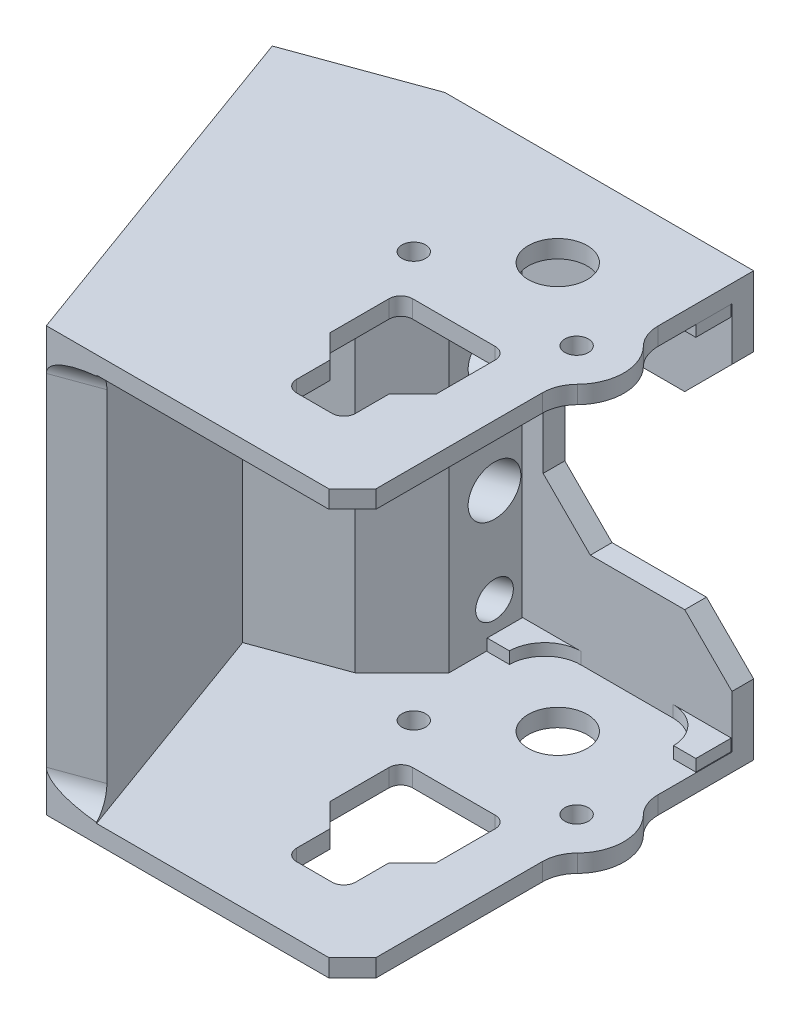
SolidWorks part; units mm, degrees
note: The reader was unsure of these and kept them because the rebuilt part matched: shared geometry of "Sketch15<2>", "Sketch16<2>".
ref_plane "Płaszczyzna przednia" through (0, 0, 0) normal (0, 0, 1) x (1, 0, 0)
ref_plane "Płaszczyzna górna" through (0, 0, 0) normal (0, 1, 0) x (1, 0, 0)
ref_plane "Płaszczyzna prawa" through (0, 0, 0) normal (1, 0, 0) x (0, 0, -1)
sketch "Sketch1" plane through (0, 0, 0) normal (0, 1, 0) x (1, 0, 0)
  line L0 (-6.9, 0) -> (6.9, 0) construction
  line L2 (-8.9, 13) -> (8.9, 13)
  line L3 (-8.9, 13) -> (-8.9, -17)
  line L4 (-8.9, -17) -> (8.9, -17)
  line L5 (8.9, 13) -> (8.9, -17)
  circle A0 centre (-6.9, 0) radius 1
  circle A1 centre (6.9, 0) radius 1
  circle A2 centre (6.9, 0) radius 2 construction
  circle A3 centre (-6.9, 0) radius 2 construction
  circle A4 centre (0, 5.3) radius 2.5
  point P4 (0, 0)
  dimension "D2" = 2
  dimension "D4" = 5
  dimension "D5" = 5.3
  dimension "D1" = 13.8
  dimension "D6" = 13
  dimension "D7" = 17
  dimension "D3" = 1
extrude "Boss-Extrude1" add sketch "Sketch1" along normal blind 1.5
sketch "Sketch2" plane through (0, 1.5, 0) normal (0, 1, 0) x (1, 0, 0)
  line L0 (0, -3.5) -> (0, 0) construction
  line L1 (-4.5, -3.5) -> (4.5, -3.5)
  line L2 (-4.5, -3.5) -> (-4.5, -9.5)
  line L3 (-4.5, -9.5) -> (4.5, -9.5)
  line L4 (4.5, -3.5) -> (4.5, -9.5)
  line L5 (0, -15.3309) -> (0, 0) construction
  line L6 (-2.5, -9.5) -> (2.5, -9.5)
  line L7 (-2.5, -9.5) -> (-2.5, -15.3309)
  line L8 (-2.5, -15.3309) -> (2.5, -15.3309)
  line L9 (2.5, -9.5) -> (2.5, -15.3309)
  dimension "D1" = 9
  dimension "D2" = 6
  dimension "D3" = 3.5
  dimension "D4" = 5
extrude "Cut-Extrude1" cut sketch "Sketch2" against normal through all contours L4 L1 L2 L3 | L9 L3 L7 L8
chamfer "Chamfer1" distance 2 angle 45 6 edges at (3.5, 0, 9.5) (2.5, 0.75, 9.5) (-3.5, 0, 9.5) (-2.5, 0.75, 9.5) (-3.5, 1.5, 9.5) (3.5, 1.5, 9.5)
fillet "Fillet1" radius 1 4 edges at (2.5, 0.75, 15.3309) (-2.5, 0.75, 15.3309) (4.5, 0.75, 3.5) (-4.5, 0.75, 3.5)
sketch "Sketch3" plane through (0, 1.5, 0) normal (0, 1, 0) x (1, 0, 0)
  line L0 (-3.9, 11.1) -> (3.9, 11.1) construction
  line L1 (-3.9, 11.1) -> (3.9, 11.1) construction
  line L2 (-6.9, 8.1) -> (-8.9, 8.1) construction
  line L3 (-8.9, 13) -> (-8.9, -17) construction
  line L4 (-8.9, 8.1) -> (-8.9, 13) construction
  line L5 (-8.9, 13) -> (8.9, 13) construction
  line L6 (8.9, 13) -> (8.9, 8.1) construction
  line L7 (8.9, -17) -> (8.9, 13) construction
  line L8 (8.9, 8.1) -> (6.9, 8.1) construction
  line L9 (8.84, 8.16) -> (6.9594, 8.16)
  line L10 (-3.9, 11.16) -> (3.9, 11.16)
  line L11 (-6.9594, 8.16) -> (-8.84, 8.16)
  line L12 (-8.84, 8.16) -> (-8.84, 12.94)
  line L13 (-8.84, 12.94) -> (8.84, 12.94)
  line L14 (8.84, 12.94) -> (8.84, 8.16)
  arc A0 (6.9, 8.1) -> (3.9, 11.1) centre (3.8989, 8.0989) ccw construction
  arc A1 (-3.9, 11.1) -> (-6.9, 8.1) centre (-3.8989, 8.0989) ccw construction
  arc A2 (6.9, 8.1) -> (3.9, 11.1) centre (3.8989, 8.0989) ccw construction
  arc A3 (-3.9, 11.1) -> (-6.9, 8.1) centre (-3.8989, 8.0989) ccw construction
  arc A4 (6.9594, 8.16) -> (3.9, 11.16) centre (3.8989, 8.0989) ccw
  arc A5 (-3.9, 11.16) -> (-6.9594, 8.16) centre (-3.8989, 8.0989) ccw
  dimension "D1" = 0.06
extrude "Boss-Extrude2" add sketch "Sketch3" along normal blind 1
ref_plane "Plane1" through (0, 17.95, 0) normal (0, 1, 0) x (1, 0, 0)
sketch "Sketch4" plane through (-8.9, 0, 0) normal (-1, 0, 0) x (0, 0, 1)
  line L0 (9.79, 17.95) -> (-9.79, 17.95) construction
  line L1 (-13, 0) -> (-1, 0)
  line L2 (-13, 0) -> (-13, 17.95)
  line L3 (-13, 17.95) -> (-1, 17.95)
  line L4 (-1, 0) -> (-1, 17.95)
  dimension "D1" = 12
extrude "Boss-Extrude3" add sketch "Sketch4" along normal blind 4
mirror "Mirror2" about plane through (0, 17.95, 0) normal (0, 1, 0) of bodies 104
sketch "Sketch5" plane through (0, 35.9, 0) normal (0, 1, 0) x (1, 0, 0)
  line L0 (-12.9, 1) -> (-17.2676, 13)
  line L1 (-17.2676, 13) -> (-12.9, 13)
  line L2 (-12.9, 13) -> (-12.9, 1)
  dimension "D1" = 20
extrude "Boss-Extrude4" add sketch "Sketch5" against normal up to surface (35.9 mm away) up to face at (0, 0, -2.8)
sketch "Sketch6" plane through (-11.0696, 0, 4.029) normal (-0.9397, 0, 0.342) x (0.342, 0, 0.9397)
  line L4 (-18.1219, 0) -> (-5.3518, 0)
  line L5 (-5.3518, 0) -> (-5.3518, 35.9)
  line L6 (-5.3518, 35.9) -> (-18.1219, 35.9)
  line L7 (-18.1219, 35.9) -> (-18.1219, 0)
  line L8 (-18.1219, 0) -> (-5.3518, 0)
  line L9 (-5.3518, 0) -> (-5.3518, 35.9)
  line L10 (-5.3518, 35.9) -> (-18.1219, 35.9)
  line L11 (-18.1219, 35.9) -> (-18.1219, 0)
  dimension "D1" = 0
extrude "Boss-Extrude5" add sketch "Sketch6" along normal blind 11.41
hole_wizard "Ø3.0 mm Dowel Holes1" positions "Sketch7" profile "Sketch9" hole size "Ø3.0" standard "DIN" end condition through all
sketch "Sketch7" plane through (-23.7268, 0, 2.6144) normal (0.9397, 0, -0.342) x (-0.342, 0, -0.9397)
  line L1 (9.6016, 17.95) -> (-0.3066, 17.95) construction
  line L2 (9.6016, 34.4) -> (9.6016, 1.5) construction
  line L3 (-0.3066, 0) -> (-0.3066, 35.9) construction
  line L4 (5.6934, 30.95) -> (5.6934, 18.95)
  line L6 (-0.3066, 0) -> (-0.3066, 35.9) construction
  point P11 (5.6934, 30.95)
  point P19 (5.6934, 4.95)
  dimension "D1" = 12
  dimension "D2" = 6
sketch "Sketch9" plane through (-25.674, 4.95, -2.7357) normal (0, 1, 0) x (0.342, 0, 0.9397)
  line L0 (0, 0) -> (0, 35.9995)
  line L1 (0, 35.9995) -> (1.5, 35.9995)
  line L2 (1.5, 35.9995) -> (1.5, 0)
  line L5 (1.5, 0) -> (0, 0)
  line L11 (0, -6.35) -> (0, 107.95) construction
  dimension "Thru Hole Dia." = 3
  dimension "Thru Hole Depth" = 35.9995
hole_wizard "Ø4.2 (4.2) Diameter Hole1" positions "Sketch10" profile "Sketch11" hole size "Ø4.2" standard "DIN" end condition through all
sketch "Sketch10" plane through (-21.7915, 0, 7.9315) normal (-0.9397, 0, 0.342) x (0.342, 0, 0.9397)
  line L0 (-11.3518, 30.95) -> (-11.3518, 22.95)
  line L1 (-11.3518, 22.95) -> (-11.3518, 30.95)
  line L3 (-11.3518, 12.95) -> (-11.3518, 4.95)
  line L5 (-11.3518, 12.95) -> (-11.3518, 4.95)
  circle A0 centre (-11.3518, 22.95) radius 4
  point P7 (-11.3518, 22.95)
  point P9 (-11.3518, 12.95)
  dimension "D2" = 8
  dimension "D1" = 10
sketch "Sketch11" plane through (-25.674, 12.95, -2.7357) normal (0, 1, 0) x (0.342, 0, 0.9397)
  line L0 (0, 0) -> (0, 35.9995)
  line L1 (0, 35.9995) -> (2.1, 35.9995)
  line L2 (2.1, 35.9995) -> (2.1, 0)
  line L5 (2.1, 0) -> (0, 0)
  line L11 (0, -6.35) -> (0, 107.95) construction
  dimension "Thru Hole Dia." = 4.2
  dimension "Thru Hole Depth" = 35.9995
sketch "Sketch12" plane through (0, 0, 17) normal (0, 0, 1) x (1, 0, 0)
  line L0 (8.9, 35.9) -> (-8.9, 35.9) construction
  line L1 (-8.9, 35.9) -> (-8.9, 34.4) construction
  line L2 (-8.9, 34.4) -> (8.9, 34.4) construction
  line L3 (8.9, 34.4) -> (8.9, 35.9) construction
  line L4 (-8.9, 0) -> (8.9, 0) construction
  line L5 (8.9, 0) -> (8.9, 1.5) construction
  line L6 (8.9, 1.5) -> (-8.9, 1.5) construction
  line L7 (-8.9, 1.5) -> (-8.9, 0) construction
  line L8 (8.9, 35.9) -> (-8.9, 35.9)
  line L9 (-8.9, 35.9) -> (-8.9, 34.4)
  line L10 (-8.9, 34.4) -> (8.9, 34.4)
  line L11 (8.9, 34.4) -> (8.9, 35.9)
  line L12 (-8.9, 0) -> (8.9, 0)
  line L13 (8.9, 0) -> (8.9, 1.5)
  line L14 (8.9, 1.5) -> (-8.9, 1.5)
  line L15 (-8.9, 1.5) -> (-8.9, 0)
extrude "Boss-Extrude6" add sketch "Sketch12" along normal blind 4
chamfer "Chamfer2" distance 2 angle 45 4 edges at (-8.9, 0.75, 21) (8.9, 0.75, 21) (8.9, 35.15, 21) (-8.9, 35.15, 21)
sketch "Sketch13" plane through (0, 0, -13) normal (0, 0, -1) x (-1, 0, 0)
  line L1 (17.2676, 0) -> (-8.9, 0)
  line L2 (17.2676, 0) -> (17.2676, 35.9)
  line L3 (17.2676, 35.9) -> (-8.9, 35.9)
  line L4 (-8.9, 0) -> (-8.9, 35.9)
extrude "Boss-Extrude7" add sketch "Sketch13" against normal up to surface (1.84 mm away) up to face at (0, 33.9, -11.16)
chamfer "Chamfer3" distance 4 angle 45 4 edges at (-8.9, 0.75, -1) (-10.9, 0, -1) (-8.9, 35.15, -1) (-10.9, 35.9, -1)
chamfer "Chamfer4" distance 4 angle 45 1 edges at (-8.9, 17.95, -1)
sketch "Sketch14" plane through (0, 0, -11.16) normal (0, 0, 1) x (1, 0, 0)
  line L0 (8.9, 17.95) -> (-8.9, 17.95) construction
  line L1 (8.9, 1.5) -> (8.9, 34.4) construction
  line L2 (-8.9, 34.4) -> (-8.9, 1.5) construction
  line L3 (8.9, 17.95) -> (8.9, 25.95)
  line L4 (8.9, 25.95) -> (-7.1, 25.95)
  line L5 (-7.1, 25.95) -> (-7.1, 9.95)
  line L6 (-7.1, 9.95) -> (8.9, 9.95)
  line L7 (8.9, 9.95) -> (8.9, 25.95)
  line M7 (8.9, 1.5) -> (8.9, 34.4)
  dimension "D1" = 8
  dimension "D2" = 16
  dimension "D3" = 16
extrude "Cut-Extrude2" cut sketch "Sketch14" against normal through all contours L0 L4 L5 M7 | L0 L5 L6 M7
chamfer "Chamfer5" distance 4 angle 45 4 edges at (-7.1, 9.95, -12.08) (-7.1, 25.95, -12.08) (8.9, 25.95, -12.08) (8.9, 9.95, -12.08)
sketch "Sketch15" plane through (0, 0, 0) normal (0, -1, 0) x (1, 0, 0)
  line L0 (8.9, 3.4641) -> (8.9, -3.4641)
  arc A0 (8.9, -3.4641) -> (8.9, 3.4641) centre (6.9, 0) ccw
  dimension "D1" = 8
extrude "Boss-Extrude8" add sketch "Sketch15" against normal up to surface (1.5 mm away) up to face at (6.9, 1.5, 1)
extrude "Boss-Extrude9" add sketch "Sketch15<2>" along direction (0, -1, 0) on the side against the normal up to surface (1.5 mm away) from surface at -34.4
sketch "Sketch15<2>" plane through (0, 0, 0) normal (0, -1, 0) x (1, 0, 0) same geometry as "Sketch15"
fillet "Fillet2" radius 3 8 edges at (-12.9, 0.75, -1) (-12.9, 35.15, -1) (-8.9, 0.75, 3) (-8.9, 35.15, 3) (8.9, 0.75, -3.4641) (8.9, 0.75, 3.4641) (8.9, 35.15, 3.4641) (8.9, 35.15, -3.4641)
sketch "Sketch16" plane through (0, 35.9, 0) normal (0, 1, 0) x (1, 0, 0)
  line L0 (-8.9, -4.2426) -> (-8.9, -19) construction
  line L1 (-11.5486, -0.3514) -> (-9.7787, -2.1213) construction
  line L2 (-23.6219, -2.9024) -> (-14.696, 0.3463) construction
  line L3 (-8.9, -4.2426) -> (-8.9, -19)
  line L4 (-11.5486, -0.3514) -> (-9.7787, -2.1213)
  line L5 (-23.6219, -2.9024) -> (-14.696, 0.3463)
  line L6 (-23.6219, -2.9024) -> (-17.0349, -21)
  line L7 (-23.6219, -2.9024) -> (-27.9895, 9.0976) construction
  line L8 (-6.9, -21) -> (-17.0349, -21)
  line L9 (-8.9, -19) -> (-6.9, -21)
  line L10 (6.9, -21) -> (-6.9, -21) construction
  arc A0 (-8.9, -4.2426) -> (-9.7787, -2.1213) centre (-11.9, -4.2426) ccw construction
  arc A1 (-11.5486, -0.3514) -> (-14.696, 0.3463) centre (-13.6699, -2.4728) ccw construction
  arc A2 (-8.9, -4.2426) -> (-9.7787, -2.1213) centre (-11.9, -4.2426) ccw
  arc A3 (-11.5486, -0.3514) -> (-14.696, 0.3463) centre (-13.6699, -2.4728) ccw
extrude "Boss-Extrude10" add sketch "Sketch16" against normal up to surface (1.5 mm away)
extrude "Boss-Extrude11" add sketch "Sketch16<2>" along normal up to surface (1.5 mm away) from surface at -35.9 up to face at (6.9, 1.5, 1) starting at face at (0, 0, -2.8)
sketch "Sketch16<2>" plane through (0, 35.9, 0) normal (0, 1, 0) x (1, 0, 0) same geometry as "Sketch16"
sketch "Sketch18" plane through (-21.7915, 0, 7.9315) normal (-0.9397, 0, 0.342) x (0.342, 0, 0.9397)
  line L0 (-5.3518, 34.4) -> (13.9073, 34.4) construction
  line L1 (-5.3518, 1.5) -> (-5.3518, 34.4) construction
  line L2 (-5.3518, 1.5) -> (13.9073, 1.5) construction
  line L3 (-5.3518, 34.4) -> (13.9073, 34.4)
  line L4 (-5.3518, 1.5) -> (-5.3518, 34.4)
  line L5 (-5.3518, 1.5) -> (13.9073, 1.5)
  line L6 (13.9073, 34.4) -> (13.9073, 1.5)
extrude "Boss-Extrude12" add sketch "Sketch18" against normal blind 4
fillet "Fillet3" radius 2 2 edges at (-15.1555, 1.5, 20.316) (-15.1555, 34.4, 20.316)
